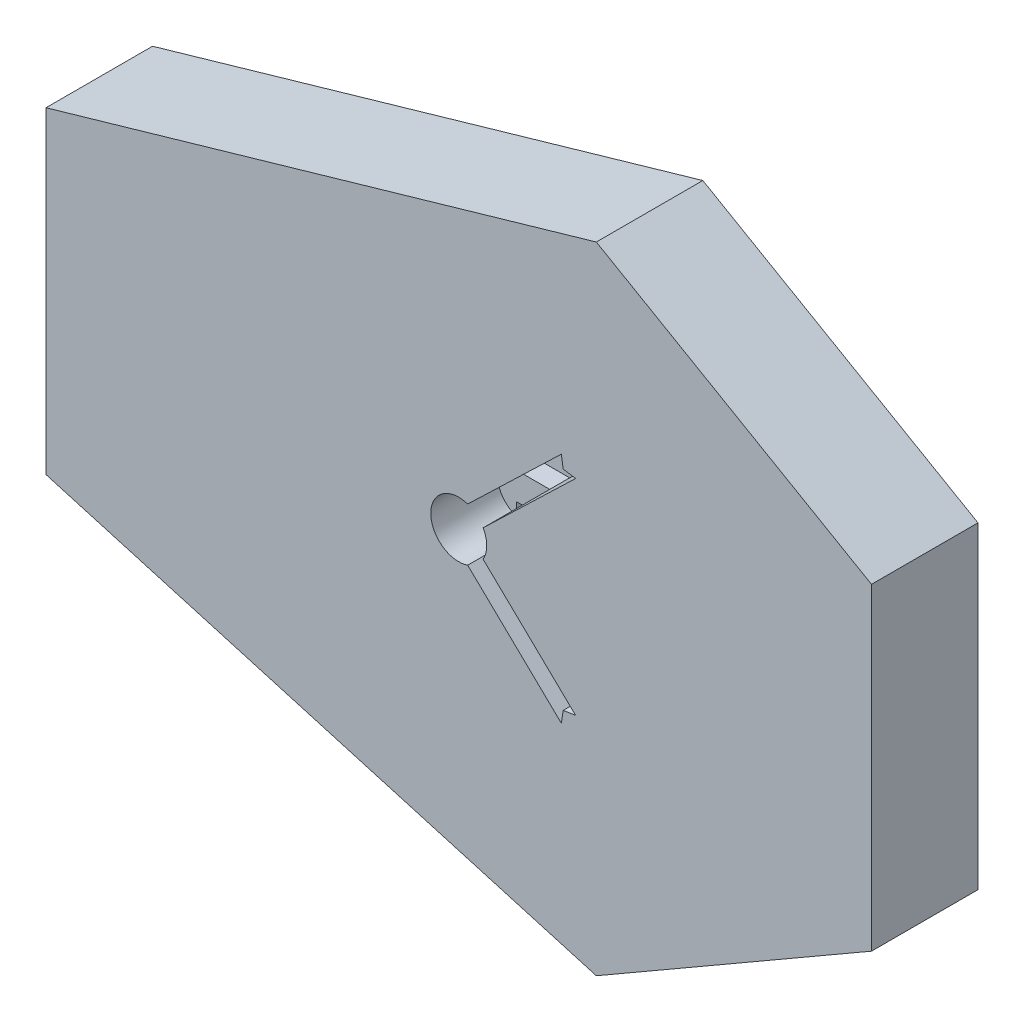
SolidWorks part; units mm, degrees
ref_plane "Front Plane" through (0, 0, 0) normal (0, 0, 1) x (1, 0, 0)
ref_plane "Top Plane" through (0, 0, 0) normal (0, 1, 0) x (1, 0, 0)
ref_plane "Right Plane" through (0, 0, 0) normal (1, 0, 0) x (0, 0, -1)
sketch "Sketch2" plane through (0, 0, 0) normal (0, 0, 1) x (1, 0, 0)
  line L0 (-36.15, 11.9319) -> (-36.15, -11.9319) construction
  line L1 (5.1833, -23.8638) -> (-36.15, -11.9319) construction
  line L2 (5.1833, -23.8638) -> (25.85, -11.9319) construction
  line L3 (25.85, -11.9319) -> (25.85, 11.9319) construction
  line L4 (25.85, 11.9319) -> (5.1833, 23.8638) construction
  line L5 (-36.15, 11.9319) -> (5.1833, 23.8638) construction
  line L6 (-36.15, 11.9319) -> (-36.15, -11.9319)
  line L7 (5.1833, -23.8638) -> (-36.15, -11.9319)
  line L8 (5.1833, -23.8638) -> (25.85, -11.9319)
  line L9 (25.85, -11.9319) -> (25.85, 11.9319)
  line L10 (25.85, 11.9319) -> (5.1833, 23.8638)
  line L11 (-36.15, 11.9319) -> (5.1833, 23.8638)
  line L12 (-34.55, -3.7) -> (-32.95, -3.7) construction
  line L13 (-32.95, -3.7) -> (-32.95, -1.5) construction
  line L14 (-32.95, -1.5) -> (-34.55, -1.5) construction
  line L15 (-34.55, -1.5) -> (-34.55, -3.7) construction
  line L16 (-34.55, 1.5) -> (-32.95, 1.5) construction
  line L17 (-32.95, 1.5) -> (-32.95, 3.7) construction
  line L18 (-32.95, 3.7) -> (-34.55, 3.7) construction
  line L19 (-34.55, 3.7) -> (-34.55, 1.5) construction
  line L20 (-34.55, -3.7) -> (-32.95, -3.7)
  line L21 (-32.95, -3.7) -> (-32.95, -1.5)
  line L22 (-32.95, -1.5) -> (-34.55, -1.5)
  line L23 (-34.55, -1.5) -> (-34.55, -3.7)
  line L24 (-34.55, 1.5) -> (-32.95, 1.5)
  line L25 (-32.95, 1.5) -> (-32.95, 3.7)
  line L26 (-32.95, 3.7) -> (-34.55, 3.7)
  line L27 (-34.55, 3.7) -> (-34.55, 1.5)
extrude "Boss-Extrude1" add sketch "Sketch2" along normal blind 1.5
sketch "Sketch4" plane through (0, 0, 1.5) normal (0, 0, 1) x (1, 0, 0)
  line L6 (5.1833, 23.8638) -> (-36.15, 11.9319)
  line L7 (-36.15, 11.9319) -> (-36.15, -11.9319)
  line L8 (-36.15, -11.9319) -> (5.1833, -23.8638)
  line L9 (5.1833, -23.8638) -> (25.85, -11.9319)
  line L10 (25.85, -11.9319) -> (25.85, 11.9319)
  line L11 (25.85, 11.9319) -> (5.1833, 23.8638)
  line L12 (5.1833, 23.8638) -> (-36.15, 11.9319)
  line L13 (-36.15, 11.9319) -> (-36.15, -11.9319)
  line L14 (-36.15, -11.9319) -> (5.1833, -23.8638)
  line L15 (5.1833, -23.8638) -> (25.85, -11.9319)
  line L16 (25.85, -11.9319) -> (25.85, 11.9319)
  line L17 (25.85, 11.9319) -> (5.1833, 23.8638)
  circle A0 centre (-5.15, 0) radius 2.1
  point P9 (-5.15, 0)
  dimension "D2" = 4.2
  dimension "D1" = 0
extrude "Boss-Extrude2" add sketch "Sketch4" along normal blind 6.5
sketch "Sketch5" plane through (0, 0, 8) normal (0, 0, 1) x (1, 0, 0)
  line L0 (-12.9946, 7.8446) -> (-17.4796, 7.1692) construction
  line L1 (-17.4796, 7.1692) -> (-17.0329, 4.2026) construction
  line L2 (-10.3578, 5.2078) -> (-17.0329, 4.2026) construction
  line L3 (-9.3526, 11.8829) -> (-10.3578, 5.2078) construction
  line L4 (-12.3192, 12.3296) -> (-9.3526, 11.8829) construction
  line L5 (-12.3192, 12.3296) -> (-12.9946, 7.8446) construction
  line L6 (-12.9946, 7.8446) -> (-17.4796, 7.1692) construction
  line L7 (-17.4796, 7.1692) -> (-17.0329, 4.2026) construction
  line L8 (-10.3578, 5.2078) -> (-17.0329, 4.2026) construction
  line L9 (-9.3526, 11.8829) -> (-10.3578, 5.2078) construction
  line L10 (-12.3192, 12.3296) -> (-9.3526, 11.8829) construction
  line L11 (-12.3192, 12.3296) -> (-12.9946, 7.8446) construction
  line L12 (-6.9826, 1.0254) -> (-13.9298, 7.7037) construction
  line L13 (-13.9298, 7.7037) -> (-12.9946, 7.8446) construction
  line L14 (-12.8578, 8.7529) -> (-5.8221, 1.9895) construction
  line L15 (-12.9946, 7.8446) -> (-12.8578, 8.7529) construction
  line L16 (-6.4, 3.7) -> (-3.9, -3.7) construction
  line L17 (-5.15, 0) -> (-5.15, 20.8808) construction
  line L18 (-12.8578, 8.7529) -> (-13.9298, 7.7037) construction
  line L19 (-13.3938, 8.2283) -> (-12.9946, 7.8446) construction
  line L20 (-6.9826, 1.0254) -> (-4.4779, 1.0254) construction
  line L21 (-4.4779, 1.0254) -> (-4.4779, 1.9895) construction
  line L22 (-4.4779, 1.9895) -> (-5.8221, 1.9895)
  line L23 (5.1833, 23.8638) -> (-36.15, 11.9319) construction
  line L24 (3.0938, 8.2283) -> (2.6946, 7.8446) construction
  line L25 (2.5578, 8.7529) -> (3.6298, 7.7037) construction
  line L26 (2.0192, 12.3296) -> (2.6946, 7.8446) construction
  line L27 (2.0192, 12.3296) -> (-0.9474, 11.8829) construction
  line L28 (-0.9474, 11.8829) -> (0.0578, 5.2078) construction
  line L29 (0.0578, 5.2078) -> (6.7329, 4.2026) construction
  line L30 (7.1796, 7.1692) -> (6.7329, 4.2026) construction
  line L31 (2.6946, 7.8446) -> (7.1796, 7.1692) construction
  line L32 (-5.8221, 1.0254) -> (-5.8221, 1.9895)
  line L33 (-3.3174, 1.0254) -> (-5.8221, 1.0254)
  line L34 (2.6946, 7.8446) -> (2.5578, 8.7529)
  line L35 (2.5578, 8.7529) -> (-4.4779, 1.9895)
  line L36 (3.6298, 7.7037) -> (2.6946, 7.8446)
  line L37 (-3.3174, 1.0254) -> (3.6298, 7.7037)
  circle A0 centre (-5.15, 0) radius 2.1 construction
  dimension "D1" = 1.5
extrude "Cut-Extrude1" cut sketch "Sketch5" against normal up to surface (6.5 mm away) up to face at (-3.05, 0, 1.5)
sketch "Sketch9" plane through (0, 0, 1.5) normal (0, 0, 1) x (1, 0, 0)
  line L8 (2.5578, 8.7529) -> (2.6946, 7.8446)
  line L9 (2.6946, 7.8446) -> (3.6298, 7.7037)
  line L10 (3.6298, 7.7037) -> (2.1327, 6.2646)
  line L11 (-3.3174, 1.0254) -> (3.6298, 7.7037) construction
  line L12 (2.1327, 6.2646) -> (1.0937, 7.3455)
  line L13 (2.5578, 8.7529) -> (-4.4779, 1.9895) construction
  line L14 (1.0937, 7.3455) -> (2.5578, 8.7529)
  dimension "D1" = 1.5
extrude "Cut-Extrude2" cut sketch "Sketch9" against normal through all
sketch "Sketch7" plane through (0, 0, 8) normal (0, 0, 1) x (1, 0, 0)
  line L0 (-7.25, 0) -> (-3.05, 0) construction
  line L1 (-5.15, 2.1) -> (-5.15, -2.1) construction
  arc A0 (-4.4779, 1.9895) -> (-3.3174, 1.0254) centre (-5.15, 0) ccw construction
ref_plane "Plane1" through (0, 0, 0) normal (0, -1, 0) x (1, 0, 0)
mirror "Mirror1" about plane through (0, 0, 0) normal (0, -1, 0) of "Cut-Extrude2", "Cut-Extrude1"
sketch "Sketch8" plane through (0, 0, 1.5) normal (0, 0, 1) x (1, 0, 0)
  line L2 (-5.8221, 1.0254) -> (-5.8221, 1.9895) construction
  line L3 (-3.3174, 1.0254) -> (-5.8221, 1.0254) construction
  line L4 (-5.8221, 1.0254) -> (-5.8221, 1.9895)
  line L5 (-3.3174, 1.0254) -> (-5.8221, 1.0254)
  line L6 (-7.25, 0) -> (-3.05, 0) construction
  line L7 (-3.3174, -1.0254) -> (-5.8221, -1.0254)
  line L8 (-5.8221, -1.0254) -> (-5.8221, -1.9895)
  arc A0 (-3.3174, -1.0254) -> (-3.3174, 1.0254) centre (-5.15, 0) ccw construction
  arc A1 (-3.3174, -1.0254) -> (-3.3174, 1.0254) centre (-5.15, 0) ccw
  arc A2 (-4.4779, 1.9895) -> (-4.4779, -1.9895) centre (-5.15, 0) ccw construction
  arc A3 (-5.8221, 1.9895) -> (-5.8221, -1.9895) centre (-5.15, 0) ccw
extrude "Boss-Extrude3" add sketch "Sketch8" along normal blind 1.5
